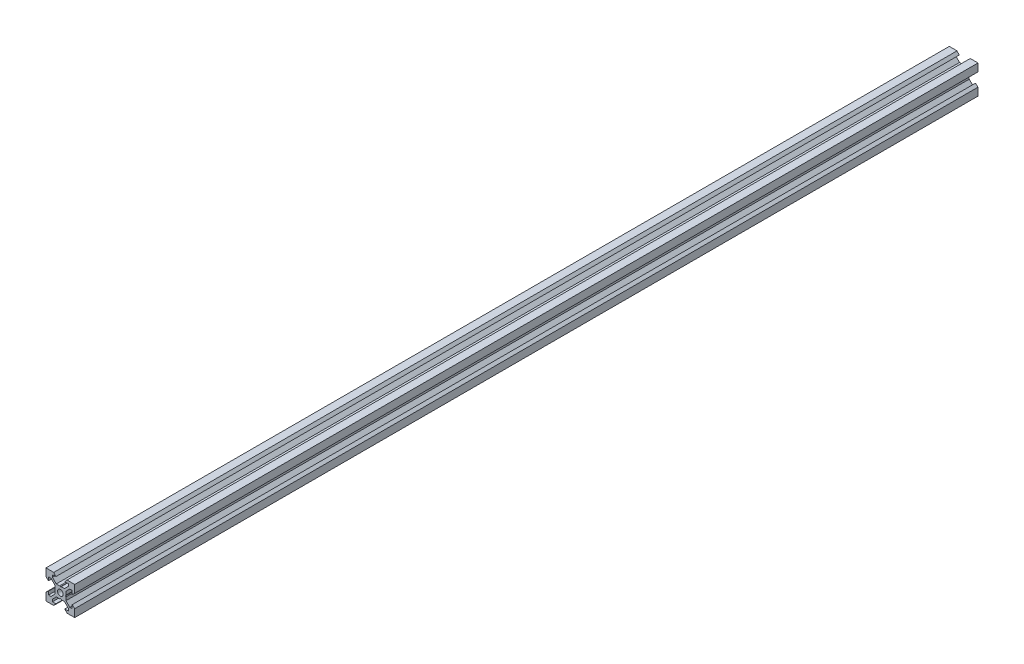
SolidWorks part; units mm, degrees
ref_plane "Front Plane" through (0, 0, 0) normal (0, 0, 1) x (1, 0, 0)
ref_plane "Top Plane" through (0, 0, 0) normal (0, 1, 0) x (1, 0, 0)
ref_plane "Right Plane" through (0, 0, 0) normal (1, 0, 0) x (0, 0, -1)
sketch "Sketch1" plane through (0, 0, 0) normal (0, 0, 1) x (1, 0, 0)
  line L0 (10, 10) -> (4.6104, 10) construction
  line L1 (10, 10) -> (10, 4.6104) construction
  line L2 (10, -10) -> (10, -4.6104) construction
  line L3 (10, -10) -> (4.6104, -10) construction
  line L4 (10, 10) -> (10, 4.6104)
  line L5 (6.5607, 5.5) -> (8.2, 5.5)
  line L6 (5.5, 8.2) -> (5.5, 6.5607)
  line L7 (10, 10) -> (4.6104, 10)
  line L8 (10, 10) -> (10, 4.6104)
  line L9 (6.5607, 5.5) -> (3.9, 2.8393)
  line L10 (5.5, 6.5607) -> (2.8393, 3.9)
  line L11 (10, 4.6104) -> (8.2, 3.1)
  line L12 (4.6104, 10) -> (3.1, 8.2)
  line L13 (8.2, 3.1) -> (8.2, 5.5)
  line L14 (3.1, 8.2) -> (5.5, 8.2)
  line L15 (-6.5607, 5.5) -> (-8.2, 5.5)
  line L16 (6.5607, -5.5) -> (8.2, -5.5)
  line L17 (3.1, -8.2) -> (5.5, -8.2)
  line L18 (8.2, -3.1) -> (8.2, -5.5)
  line L19 (4.6104, -10) -> (3.1, -8.2)
  line L20 (10, -4.6104) -> (8.2, -3.1)
  line L21 (0.5196, -3.9) -> (0, -3.6)
  line L22 (0.5196, 3.9) -> (0, 3.6)
  line L23 (3.6, 0) -> (3.9, -0.5196)
  line L24 (3.9, 0.5196) -> (3.6, 0)
  line L25 (3.9, 0.5196) -> (3.9, 2.8393)
  line L26 (2.8393, 3.9) -> (0.5196, 3.9)
  line L27 (3.9, -2.8393) -> (3.9, -0.5196)
  line L28 (2.8393, -3.9) -> (0.5196, -3.9)
  line L29 (5.5, -6.5607) -> (2.8393, -3.9)
  line L30 (6.5607, -5.5) -> (3.9, -2.8393)
  line L31 (10, -10) -> (10, -4.6104)
  line L32 (10, -10) -> (4.6104, -10)
  line L33 (5.5, -8.2) -> (5.5, -6.5607)
  line L34 (-6.5607, -5.5) -> (-8.2, -5.5)
  line L35 (10, -10) -> (10, -4.6104)
  line L36 (0, 0) -> (0, 8.2) construction
  line L37 (-10, -10) -> (-4.6104, -10) construction
  line L38 (-10, -10) -> (-10, -4.6104) construction
  line L39 (-10, 10) -> (-10, 4.6104) construction
  line L40 (-10, 10) -> (-4.6104, 10) construction
  line L41 (-10, -10) -> (-10, -4.6104)
  line L43 (-5.5, -8.2) -> (-5.5, -6.5607)
  line L44 (-10, -10) -> (-4.6104, -10)
  line L45 (-10, -10) -> (-10, -4.6104)
  line L46 (-6.5607, -5.5) -> (-3.9, -2.8393)
  line L47 (-5.5, -6.5607) -> (-2.8393, -3.9)
  line L48 (-2.8393, -3.9) -> (-0.5196, -3.9)
  line L49 (-3.9, -2.8393) -> (-3.9, -0.5196)
  line L50 (-2.8393, 3.9) -> (-0.5196, 3.9)
  line L51 (-3.9, 0.5196) -> (-3.9, 2.8393)
  line L52 (-3.9, 0.5196) -> (-3.6, 0)
  line L53 (-3.6, 0) -> (-3.9, -0.5196)
  line L54 (-0.5196, 3.9) -> (0, 3.6)
  line L55 (-0.5196, -3.9) -> (0, -3.6)
  line L56 (-10, -4.6104) -> (-8.2, -3.1)
  line L57 (-4.6104, -10) -> (-3.1, -8.2)
  line L58 (-8.2, -3.1) -> (-8.2, -5.5)
  line L59 (-3.1, -8.2) -> (-5.5, -8.2)
  line L60 (-10, -10) -> (10, -10) construction
  line L61 (-10, -10) -> (-10, 10) construction
  line L62 (-3.1, 8.2) -> (-5.5, 8.2)
  line L63 (-8.2, 3.1) -> (-8.2, 5.5)
  line L64 (-4.6104, 10) -> (-3.1, 8.2)
  line L65 (-10, 4.6104) -> (-8.2, 3.1)
  line L66 (-5.5, 6.5607) -> (-2.8393, 3.9)
  line L67 (-6.5607, 5.5) -> (-3.9, 2.8393)
  line L68 (-10, 10) -> (-10, 4.6104)
  line L69 (-10, 10) -> (-4.6104, 10)
  line L70 (-5.5, 8.2) -> (-5.5, 6.5607)
  line L71 (-10, 10) -> (10, 10) construction
  line L72 (-10, 10) -> (-10, 4.6104)
  line L73 (10, -10) -> (10, 10) construction
  line L74 (-10, -10) -> (10, 10) construction
  line L75 (-10, 10) -> (10, -10) construction
  circle A0 centre (0, 0) radius 2
  dimension "D7" = 4
  dimension "D1" = 20
  dimension "D2" = 5.3896
  dimension "D3" = 4.5
  dimension "D4" = 50
  dimension "D5" = 1.8
  dimension "D6" = 1.5104
  dimension "D8" = 5.5
  dimension "D9" = 120
  dimension "D10" = 0.3
  dimension "D11" = 2.3197
  dimension "D12" = 7.8
  dimension "D13" = 7.8
  dimension "D14" = 1.5
  dimension "D15" = 2.6607
extrude "Boss-Extrude1" add sketch "Sketch1" along normal mid plane 629.15 contours L70 L62 L64 L69 L68 L65 L63 L15 L67 L51 L52 L53 L49 L46 L34 L58 L56 L41 L44 L57 L59 L43 L47 L48 L55 L21 L28 L29 L33 L17 L19 L32 L31 L20 L18 L16 L30 L27 L23 L24 L25 L9 L5 L13 L11 L4 L7 L12 L14 L6 L10 region at (9.7172, 7.3052, 0)
